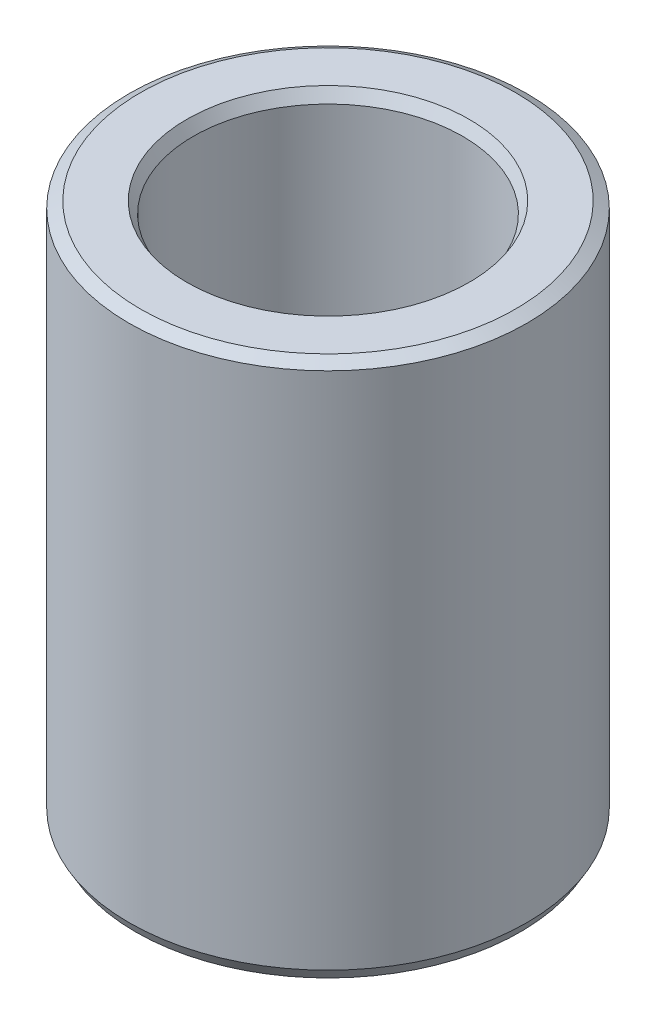
SolidWorks part; units mm, degrees
ref_plane "Front Plane" through (0, 0, 0) normal (0, 0, 1) x (1, 0, 0)
ref_plane "Top Plane" through (0, 0, 0) normal (0, 1, 0) x (1, 0, 0)
ref_plane "Right Plane" through (0, 0, 0) normal (1, 0, 0) x (0, 0, -1)
sketch "Sketch1" plane through (0, 0, 0) normal (0, 1, 0) x (1, 0, 0)
  circle A0 centre (0, 0) radius 57.5
  dimension "SLEEVE_OD" = 115
extrude "Boss-Extrude1" add sketch "Sketch1" along normal blind 155.2366
sketch "Sketch2" plane through (0, 0, 0) normal (0, 1, 0) x (1, 0, 0)
  circle A0 centre (0, 0) radius 38.9271
  dimension "BORE_D" = 77.8542
extrude "Cut-Extrude1" cut sketch "Sketch2" along normal through all
chamfer "Chamfer1" distance 1.9022 angle 60 4 edges at (0, 155.2366, 38.9271) (0, 0, 38.9271) (0, 0, 57.5) (0, 155.2366, 57.5) first distance on face at (0, 155.2366, 38.9271) first distance on face at (0, 0, 38.9271) first distance on face at (0, 155.2366, 57.5)
